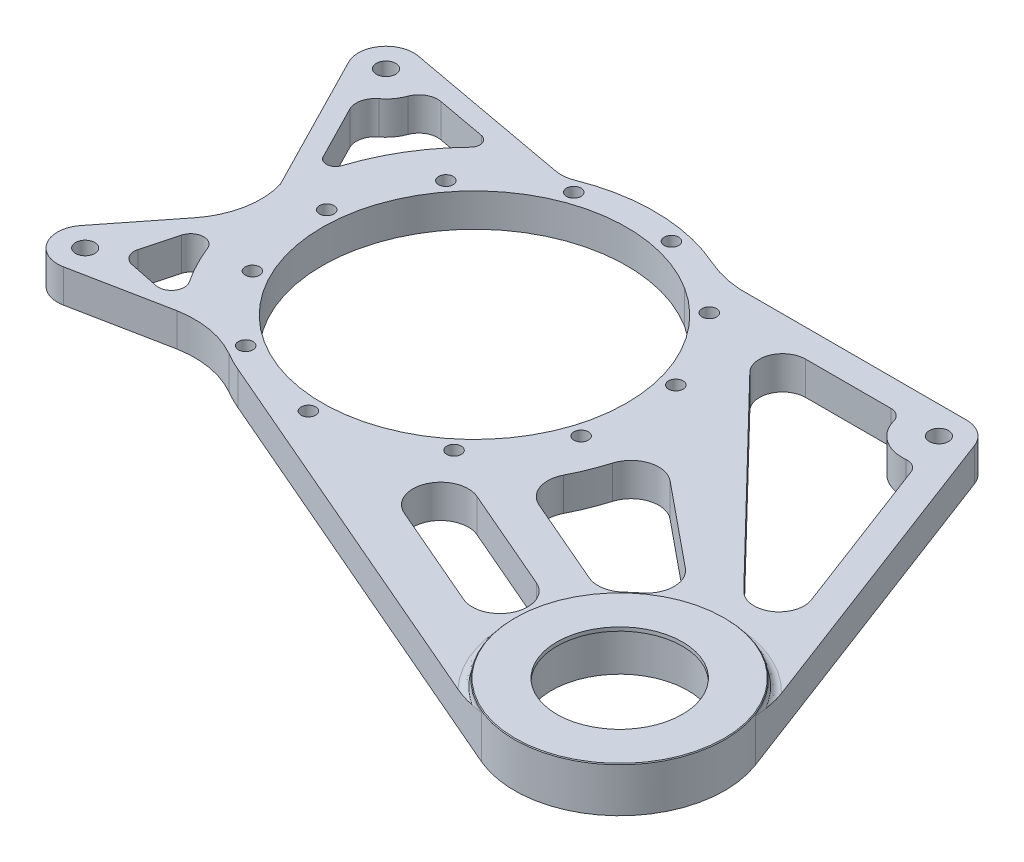
SolidWorks part; units mm, degrees
material "7075-T6 (SN)"
ref_plane "X-Y Datum" through (0, 0, 0) normal (0, 0, 1) x (1, 0, 0)
ref_plane "X-Z Datum" through (0, 0, 0) normal (0, 1, 0) x (1, 0, 0)
ref_plane "Y-Z Datum" through (0, 0, 0) normal (1, 0, 0) x (0, 0, -1)
sketch "Sketch1" plane through (0, 0, 0) normal (0, 1, 0) x (1, 0, 0)
  line L0 (-452.4939, -193.2569) -> (-599.8423, -129.6662)
  line L3 (-568.96, 0) -> (-463.042, 0) construction
  line L4 (-685.8, 0) -> (-568.96, 0) construction
  line L5 (-685.8, -143.2733) -> (-685.8, 0) construction
  line L6 (-685.8, -143.2733) -> (-575.31, -72.8215) construction
  line L7 (-575.31, -72.8215) -> (-438.15, -160.02) construction
  line L8 (-685.8, -1.6598) -> (-575.31, -72.8215) construction
  line L9 (-537.4328, -19.4168) -> (-459.3604, -19.4168)
  line L14 (-652.4813, -91.9261) -> (-669.8039, -113.9002)
  line L15 (-673.1, -130.5733) -> (-698.5, -130.5733) construction
  line L16 (-673.1, -130.5733) -> (-673.1, -155.9733) construction
  line L17 (-673.1, -155.9733) -> (-698.5, -155.9733) construction
  line L18 (-698.5, -130.5733) -> (-698.5, -155.9733) construction
  line L19 (-673.1, -130.5733) -> (-698.5, -155.9733) construction
  line L20 (-673.1, -155.9733) -> (-698.5, -130.5733) construction
  line L21 (-627.8464, -122.6884) -> (-660.4758, -129.1411)
  line L22 (-662.2354, -5.2529) -> (-604.1922, -15.9133)
  line L23 (-672.4346, -18.9616) -> (-647.7651, -67.1526)
  line L25 (-673.1, -12.7) -> (-698.5, -12.7) construction
  line L26 (-673.1, -12.7) -> (-673.1, 12.7) construction
  line L27 (-673.1, 12.7) -> (-698.5, 12.7) construction
  line L28 (-698.5, -12.7) -> (-698.5, 12.7) construction
  line L29 (-673.1, -12.7) -> (-698.5, 12.7) construction
  line L30 (-673.1, 12.7) -> (-698.5, -12.7) construction
  line L32 (-685.8, -130.5733) -> (-673.1, -130.5733) construction
  line L33 (-685.8, -129.1488) -> (-685.8, -130.5733) construction
  line L34 (-668.5282, -112.57) -> (-684.4718, -126.258) construction
  line L35 (-667.4361, -138.3507) -> (-655.5968, -126.5405) construction
  line L36 (-673.1, -139.4633) -> (-670.1269, -139.4633) construction
  line L37 (-673.1, -130.5733) -> (-673.1, -139.4633) construction
  line L38 (-685.8, -130.5733) -> (-673.1, -130.5733) construction
  line L39 (-685.8, -129.1488) -> (-685.8, -130.5733) construction
  line L40 (-668.5282, -112.57) -> (-684.4718, -126.258) construction
  line L41 (-667.4361, -138.3507) -> (-655.5968, -126.5405) construction
  line L42 (-673.1, -139.4633) -> (-670.1269, -139.4633) construction
  line L43 (-673.1, -130.5733) -> (-673.1, -139.4633) construction
  line L44 (-463.042, 0) -> (-463.042, -3.81) construction
  line L45 (-575.31, -72.8215) -> (-459.3604, -28.9418) construction
  line L46 (-450.455, -25.5624) -> (-404.305, -147.1765)
  line L47 (-575.31, -72.8215) -> (-575.31, -78.4445) construction
  line L48 (-655.8976, -11.4734) -> (-668.4375, -1.9195)
  line L49 (-670.3617, -1.27) -> (-673.1, -1.27)
  line L50 (-673.1, -1.27) -> (-673.1, -12.7)
  line L51 (-673.1, -12.7) -> (-684.53, -12.7)
  line L52 (-684.53, -12.7) -> (-684.53, -14.7065)
  line L53 (-682.9809, -17.4336) -> (-666.5478, -27.2313)
  line L56 (-673.1, -1.27) -> (-673.1, -12.7) construction
  line L57 (-673.1, -12.7) -> (-684.53, -12.7) construction
  circle A13 centre (-438.15, -160.02) radius 23.5
  circle A17 centre (-575.31, -72.8215) radius 61.9125 construction
  circle A18 centre (-575.31, -72.8215) radius 52.3875
  circle A29 centre (-438.15, -160.02) radius 36.2 construction
  arc A36 (-588.7133, -12.3772) -> (-550.1347, -16.2586) centre (-575.31, -72.8215) cw
  arc A38 (-627.8464, -122.6884) -> (-606.238, -126.4556) centre (-622.1949, -154.1272) cw
  circle A39 centre (-662.3237, -119.797) radius 3.3
  arc A45 (-684.4718, -126.258) -> (-685.8, -129.1488) centre (-681.99, -129.1488) ccw construction
  circle A46 centre (-662.3237, -119.797) radius 3.3
  circle A47 centre (-662.3237, -119.797) radius 3.3 construction
  arc A48 (-655.5968, -126.5405) -> (-668.5282, -112.57) centre (-662.3237, -119.797) ccw construction
  arc A49 (-670.1269, -139.4633) -> (-667.4361, -138.3507) centre (-670.1269, -135.6533) ccw construction
  arc A50 (-684.4718, -126.258) -> (-685.8, -129.1488) centre (-681.99, -129.1488) ccw construction
  arc A51 (-655.5968, -126.5405) -> (-668.5282, -112.57) centre (-662.3237, -119.797) ccw construction
  arc A52 (-670.1269, -139.4633) -> (-667.4361, -138.3507) centre (-670.1269, -135.6533) ccw construction
  circle A53 centre (-662.3237, -119.797) radius 9.525 construction
  arc A54 (-599.8423, -129.6662) -> (-606.238, -126.4556) centre (-575.31, -72.8215) cw
  arc A55 (-669.8039, -113.9002) -> (-660.4758, -129.1411) centre (-662.3237, -119.797) ccw
  circle A57 centre (-602.253, -5.3549) radius 10.7351 construction
  arc A58 (-588.7133, -12.3772) -> (-598.2717, -15.3244) centre (-575.31, -72.8215) ccw
  arc A59 (-668.4375, -1.9195) -> (-670.3617, -1.27) centre (-670.3617, -4.445) ccw
  arc A60 (-684.53, -14.7065) -> (-682.9809, -17.4336) centre (-681.355, -14.7065) ccw
  arc A61 (-666.5478, -27.2313) -> (-655.8976, -11.4734) centre (-661.67, -19.05) ccw
  arc A65 (-647.7651, -67.1526) -> (-652.4813, -91.9261) centre (-673.9475, -75.0039) cw
  arc A67 (-598.2717, -15.3244) -> (-604.1922, -15.9133) centre (-602.253, -5.3549) cw
  circle A68 centre (-463.042, -3.81) radius 12.7 construction
  circle A69 centre (-459.3604, -28.9418) radius 3.3
  circle A70 centre (-459.3604, -28.9418) radius 9.525 construction
  arc A71 (-550.1347, -16.2586) -> (-537.4328, -19.4168) centre (-534.8559, 18.0692) ccw
  arc A72 (-459.3604, -19.4168) -> (-450.455, -25.5624) centre (-459.3604, -28.9418) cw
  arc A73 (-452.4939, -193.2569) -> (-404.305, -147.1765) centre (-438.15, -160.02) ccw
  circle A74 centre (-685.8, -1.6598) radius 12.7 construction
  circle A75 centre (-663.956, -14.6213) radius 3.3
  circle A76 centre (-663.956, -14.6213) radius 9.525 construction
  arc A77 (-662.2354, -5.2529) -> (-672.4346, -18.9616) centre (-663.956, -14.6213) ccw
  dimension "D7" = 25.4
  dimension "D10" = 123.825
  dimension "D11" = 104.775
  dimension "D12" = 47
  dimension "D13" = 72.4
  dimension "D15" = 26.943
  dimension "D18" = 43.8797
  dimension "D24" = 31.9428
  dimension "D25" = 32.6295
  dimension "D26" = 9.344
  dimension "D29" = 21.9741
  dimension "D33" = 27.3342
  dimension "D34" = 21.844
  dimension "D23" = 19.05
  dimension "D32" = 25.4
  dimension "D38" = 3.81
  dimension "D28" = 21.4701
  dimension "D19" = 37.5744
  dimension "D17" = 25.4
  dimension "D22" = 19.05
  dimension "D1" = 685.8
  dimension "D2" = 116.84
  dimension "D3" = 222.758
  dimension "D5" = 160.02
  dimension "D6" = 117.8733
  dimension "D8" = 72.8215
  dimension "D9" = 110.49
  dimension "D14" = 25.4
  dimension "D16" = 25.1753
  dimension "D20" = 1.6598
  dimension "D21" = 25.4
  dimension "D27" = 247.65
  dimension "D30" = 7.4802
  dimension "D31" = 0
  dimension "D36" = 3.8814
  dimension "D37" = 25.4
  dimension "D43" = 0
extrude "Boss-Extrude1" add sketch "Sketch1" along normal mid plane 11.43
sketch "Sketch2" plane through (0, 5.715, 0) normal (0, 1, 0) x (1, 0, 0)
  circle A1 centre (-438.15, -160.02) radius 23.5 construction
  circle A2 centre (-438.15, -160.02) radius 36.2
  circle A3 centre (-438.15, -160.02) radius 36.2
  circle A4 centre (-438.15, -160.02) radius 23.5
  circle A5 centre (-438.15, -160.02) radius 21.595
  circle M23 centre (-438.15, -160.02) radius 23.5
  dimension "D1" = 12.7
  dimension "D2" = 1.905
extrude "Boss-Extrude2" add sketch "Sketch2" along normal blind 4.0116 contours A3 M23 | A5 M23 region at (-473.3261, 5.715, 160.02) region at (-460.9853, 5.715, 160.02)
fillet "Fillet1" radius 3.175 1 edges at (-463.1685, 5.715, 133.8567)
sketch "Sketch6" plane through (0, 5.715, 0) normal (0, -1, 0) x (1, 0, 0)
  circle A0 centre (-438.15, 160.02) radius 23.5 construction
  circle A1 centre (-438.15, 160.02) radius 21.595
  circle A2 centre (-438.15, 160.02) radius 21.595
  circle A3 centre (-438.15, 160.02) radius 23.5
  dimension "D1" = 0
extrude "Cut-Extrude1" cut sketch "Sketch6" against normal blind 2.7382
ref_point "Point1"
ref_point "Point2"
ref_plane "Plane1" through (-438.15, 1.3691, 160.02) normal (0.8439, 0, 0.5365) x (0.5365, 0, -0.8439)
ref_plane "Plane2" through (-376.7454, 0, -239.5133) normal (0.8439, 0, 0.5365) x (0.5365, 0, -0.8439)
split line "Split Line1"
split line "Split Line2"
sketch "Sketch8" plane through (0, -5.715, 0) normal (0, -1, 0) x (1, 0, 0)
  circle A0 centre (-575.31, 72.8215) radius 61.9125 construction
  circle A1 centre (-575.31, 72.8215) radius 61.9125
split line "Split Line5"
sketch "Sketch11" plane through (0, -5.715, 0) normal (0, -1, 0) x (1, 0, 0)
  line L0 (-432.5065, 99.7069) -> (-453.4854, 44.4233)
  line L1 (-505.1999, 28.9418) -> (-475.9191, 28.9418)
  line L2 (-446.7272, 108.7426) -> (-510.9245, 42.4551)
  line L6 (-459.3604, 19.4168) -> (-537.4328, 19.4168) construction
  line L8 (-520.863, 126.4041) -> (-484.9545, 141.901)
  line L9 (-507.6372, 118.2797) -> (-477.2649, 131.3874)
  line L10 (-492.3337, 88.4924) -> (-463.6054, 111.9621)
  line L19 (-658.1742, 32.8834) -> (-648.5837, 51.6181)
  line L20 (-644.8026, 14.9109) -> (-627.7247, 18.0475)
  line L21 (-672.4346, 18.9616) -> (-647.7651, 67.1526) construction
  line L22 (-662.2354, 5.2529) -> (-604.1922, 15.9133) construction
  line L23 (-672.4346, 18.9616) -> (-647.7651, 67.1526) construction
  line L24 (-662.2354, 5.2529) -> (-604.1922, 15.9133) construction
  line L25 (-662.3237, 119.797) -> (-575.31, 72.8215) construction
  line L26 (-652.7583, 111.1604) -> (-649.5762, 99.3396)
  line L27 (-649.3552, 116.671) -> (-638.88, 118.8094)
  line L28 (-528.4114, 143.8948) -> (-492.5029, 159.3917)
  line L29 (-599.8423, 129.6662) -> (-452.4939, 193.2569) construction
  line L30 (-404.305, 147.1765) -> (-450.455, 25.5624) construction
  circle A0 centre (-440.5484, 102.7586) radius 8.6015 construction
  circle A1 centre (-505.1999, 36.911) radius 7.9692 construction
  circle A2 centre (-475.9191, 33.3868) radius 4.445 construction
  circle A3 centre (-457.6413, 46.0004) radius 4.445 construction
  arc A4 (-475.9191, 28.9418) -> (-471.6261, 32.2344) centre (-475.9191, 33.3868) ccw
  circle A6 centre (-575.31, 72.8215) radius 70.8025
  circle A7 centre (-575.31, 72.8215) radius 70.8025 construction
  circle A9 centre (-459.3604, 28.9418) radius 12.7 construction
  arc A10 (-471.6261, 32.2344) -> (-458.087, 41.5778) centre (-459.3604, 28.9418) cw
  arc A11 (-453.4854, 44.4233) -> (-458.087, 41.5778) centre (-457.6413, 46.0004) cw
  arc A12 (-432.5065, 99.7069) -> (-446.7272, 108.7426) centre (-440.5484, 102.7586) ccw
  arc A13 (-505.1999, 28.9418) -> (-510.9245, 42.4551) centre (-505.1999, 36.911) cw
  circle A14 centre (-524.6372, 135.1494) radius 9.525 construction
  circle A15 centre (-488.7287, 150.6463) radius 9.525 construction
  circle A16 centre (-503.863, 109.5343) radius 9.525 construction
  circle A17 centre (-473.4907, 122.642) radius 9.525 construction
  arc A19 (-512.335, 105.181) -> (-507.4844, 93.1359) centre (-575.31, 72.8215) cw
  circle A20 centre (-498.3598, 95.8688) radius 9.525 construction
  arc A23 (-528.4114, 143.8948) -> (-520.863, 126.4041) centre (-524.6372, 135.1494) ccw
  arc A24 (-492.5029, 159.3917) -> (-484.9545, 141.901) centre (-488.7287, 150.6463) cw
  arc A25 (-507.6372, 118.2797) -> (-512.335, 105.181) centre (-503.863, 109.5343) ccw
  arc A26 (-507.4844, 93.1359) -> (-492.3337, 88.4924) centre (-498.3598, 95.8688) ccw
  circle A28 centre (-469.6315, 119.3385) radius 9.525 construction
  arc A29 (-466.9467, 129.5632) -> (-463.8022, 126.8714) centre (-438.15, 160.02) ccw
  arc A30 (-477.2649, 131.3874) -> (-466.9467, 129.5632) centre (-473.4907, 122.642) cw
  arc A31 (-463.8022, 126.8714) -> (-463.6054, 111.9621) centre (-469.6315, 119.3385) cw
  arc A34 (-468.5591, 188.8671) -> (-407.9721, 130.9312) centre (-438.15, 160.02) ccw
  arc A35 (-468.5591, 188.8671) -> (-407.9721, 130.9312) centre (-438.15, 160.02) ccw construction
  circle A52 centre (-652.4088, 29.932) radius 6.477 construction
  circle A53 centre (-645.9727, 21.2814) radius 6.477 construction
  circle A54 centre (-645.7462, 50.1656) radius 3.1877 construction
  circle A55 centre (-628.3005, 21.1828) radius 3.1877 construction
  arc A57 (-642.7116, 51.1417) -> (-626.0175, 23.4075) centre (-575.31, 72.8215) ccw
  arc A60 (-642.7116, 51.1417) -> (-648.5837, 51.6181) centre (-645.7462, 50.1656) ccw
  arc A61 (-626.0175, 23.4075) -> (-627.7247, 18.0475) centre (-628.3005, 21.1828) cw
  circle A63 centre (-648.4662, 112.3158) radius 4.445 construction
  circle A64 centre (-637.9909, 114.4542) radius 4.445 construction
  circle A65 centre (-645.284, 100.4951) radius 4.445 construction
  arc A66 (-641.1505, 98.8604) -> (-634.2883, 111.9949) centre (-575.31, 72.8215) cw
  arc A67 (-652.7583, 111.1604) -> (-649.3552, 116.671) centre (-648.4662, 112.3158) cw
  arc A68 (-638.88, 118.8094) -> (-634.2883, 111.9949) centre (-637.9909, 114.4542) cw
  arc A69 (-641.1505, 98.8604) -> (-649.5762, 99.3396) centre (-645.284, 100.4951) cw
  circle A70 centre (-459.3604, 28.9418) radius 3.3 construction
  circle A71 centre (-459.3604, 28.9418) radius 3.3 construction
  arc A74 (-656.3088, 24.7608) -> (-652.0465, 19.0319) centre (-663.956, 14.6213) cw
  circle A75 centre (-663.956, 14.6213) radius 12.7
  circle A76 centre (-663.956, 14.6213) radius 12.7 construction
  arc A77 (-658.1742, 32.8834) -> (-656.3088, 24.7608) centre (-652.4088, 29.932) ccw
  arc A78 (-652.0465, 19.0319) -> (-644.8026, 14.9109) centre (-645.9727, 21.2814) ccw
  dimension "D3" = 8.89
  dimension "D6" = 25.4
  dimension "D10" = 19.05
  dimension "D15" = 12.954
  dimension "D16" = 6.3754
  dimension "D19" = 8.89
  dimension "D4" = 9.525
  dimension "D5" = 9.525
  dimension "D7" = 73.8169
  dimension "D8" = 29.0831
  dimension "D9" = 15.24
  dimension "D11" = 12.7
  dimension "D12" = 14.732
  dimension "D14" = 5.08
  dimension "D17" = 6.35
  dimension "D18" = 6.35
  dimension "D20" = 8.89
  dimension "D21" = 6.858
  dimension "D22" = 15.748
  dimension "D23" = 45.8396
  dimension "D1" = 8.89
  dimension "D13" = 2.54
  dimension "D24" = 3.175
extrude "Cut-Extrude3" cut sketch "Sketch11" against normal through all
sketch "Sketch12" plane through (0, -5.715, 0) normal (0, -1, 0) x (1, 0, 0)
  line L0 (-575.31, 72.8215) -> (-575.31, 159.4351) construction
  line L1 (-685.8, 143.2733) -> (-685.8, 0) construction
  line L2 (-685.8, 143.2733) -> (-685.8, 0)
  arc A0 (-603.416, 117.0312) -> (-547.204, 28.6117) centre (-575.31, 72.8215) ccw construction
  arc A1 (-547.204, 28.6117) -> (-603.416, 117.0312) centre (-575.31, 72.8215) ccw construction
  arc A2 (-603.416, 117.0312) -> (-547.204, 28.6117) centre (-575.31, 72.8215) ccw construction
  arc A3 (-547.204, 28.6117) -> (-603.416, 117.0312) centre (-575.31, 72.8215) ccw construction
  circle A4 centre (-575.31, 129.9715) radius 4.7625 construction
  arc A6 (-550.1347, 16.2586) -> (-599.8423, 129.6662) centre (-575.31, 72.8215) ccw construction
hole_wizard "Ø5.0mm Dowel Hole1" positions "Sketch13" profile "Sketch14" hole size "Ø5.0" standard "ANSI Metric" end condition through all
sketch "Sketch13" plane through (0, -5.715, 0) normal (0, -1, 0) x (-1, 0, 0)
  point P0 (575.31, -129.9715)
sketch "Sketch14" plane through (-575.31, -5.715, 129.9715) normal (1, 0, 0) x (0, 0, -1)
  line L0 (0, 0) -> (0, 15.4416)
  line L1 (0, 15.4416) -> (2.5, 15.4416)
  line L2 (2.5, 15.4416) -> (2.5, 0.025)
  line L3 (2.5, 0.025) -> (2.525, 0)
  line L5 (2.525, 0) -> (0, 0)
  line L6 (-2.5, 0.025) -> (-2.525, 0) construction
  line L11 (0, -6.35) -> (0, 107.95) construction
  dimension "Thru Hole Dia." = 5
  dimension "Thru Hole Depth" = 15.4416
  dimension "Near C'Sink Dia." = 5.05
  dimension "Near C'Sink Angle" = 90
pattern_circular "CirPattern1" count 11 every 32 about axis through (-575.31, 5.715, 72.8215) along (0, -1, 0) of "Ø5.0mm Dowel Hole1"
chamfer "Chamfer1" distance 0.254 angle 45 1 edges at (-438.15, 9.7266, 196.22)
